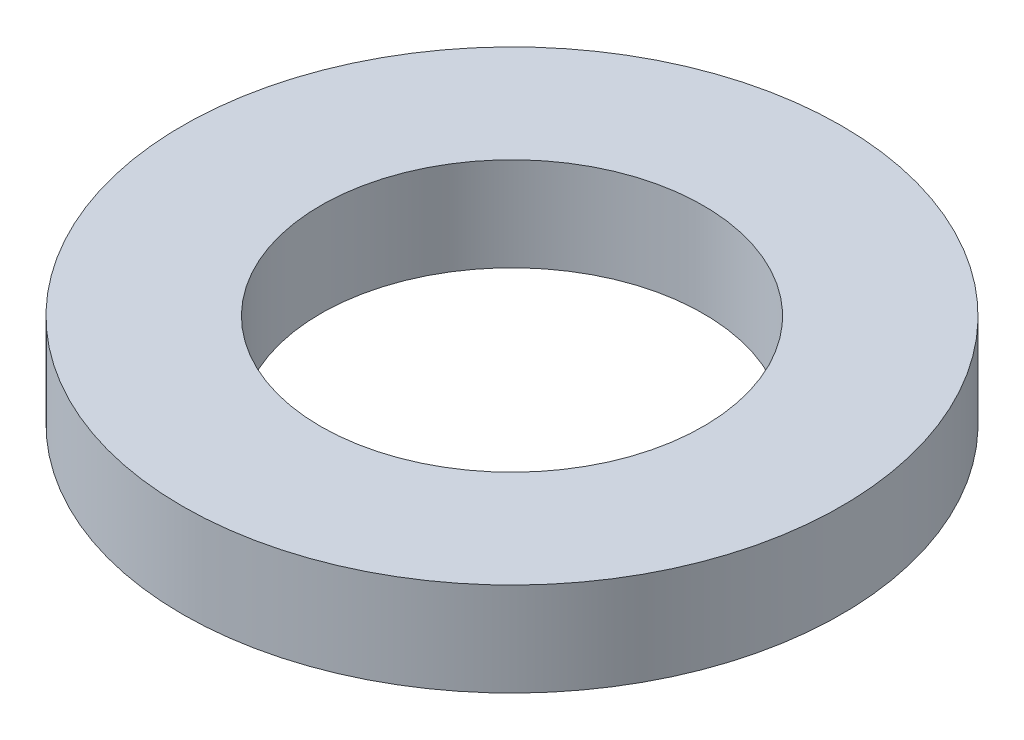
SolidWorks part; units mm, degrees
ref_plane "Front Plane" through (0, 0, 0) normal (0, 0, 1) x (1, 0, 0)
ref_plane "Top Plane" through (0, 0, 0) normal (0, 1, 0) x (1, 0, 0)
ref_plane "Right Plane" through (0, 0, 0) normal (1, 0, 0) x (0, 0, -1)
sketch "Sketch1" plane through (0, 0, 0) normal (0, 1, 0) x (1, 0, 0)
  circle A0 centre (0, 0) radius 77.5
  dimension "FLANGE_OD" = 155
extrude "Boss-Extrude1" add sketch "Sketch1" along normal blind 22
sketch "Sketch2" plane through (0, 0, 0) normal (0, 1, 0) x (1, 0, 0)
  circle A0 centre (0, 0) radius 45
  dimension "BORE_D" = 90
extrude "Cut-Extrude1" cut sketch "Sketch2" along normal through all
sketch "Sketch3" plane through (0, 22, 0) normal (0, 1, 0) x (1, 0, 0)
  circle A0 centre (0, 0) radius 34.1458 construction
  circle A1 centre (-34.1458, 0) radius 2.0862
  dimension "BOLT_D" = 4.1723
  dimension "BOLT_PCD" = 68.2916
extrude "Cut-Extrude2" cut sketch "Sketch3" against normal blind 19.2402 rebuild error yes
pattern_circular "CirPattern1" count 3 over 360 rebuild error yes
